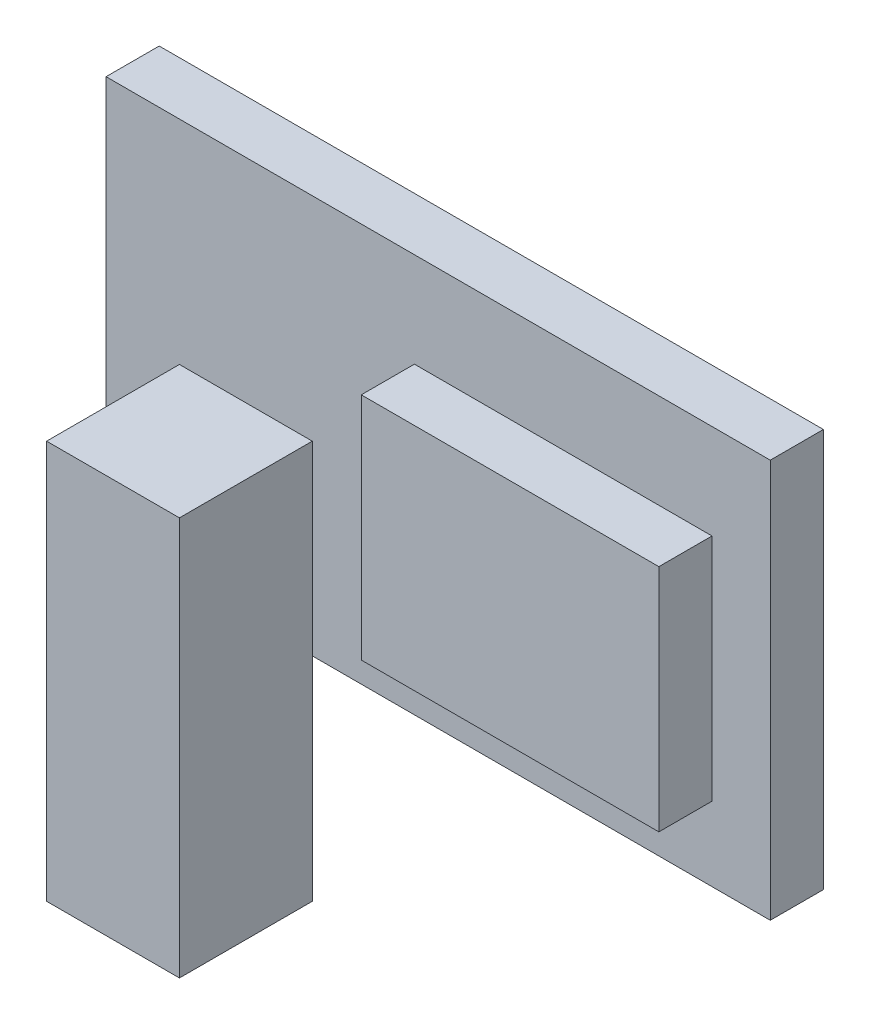
SolidWorks part; units mm, degrees
ref_plane "前视基准面" through (0, 0, 0) normal (0, 0, 1) x (1, 0, 0)
ref_plane "上视基准面" through (0, 0, 0) normal (0, 1, 0) x (1, 0, 0)
ref_plane "右视基准面" through (0, 0, 0) normal (1, 0, 0) x (0, 0, -1)
sketch "草图2" plane through (0, 0, 0) normal (0, 0, 1) x (1, 0, 0)
  line L1 (-14.3456, 4.0965) -> (10.6544, 4.0965)
  line L2 (-14.3456, 4.0965) -> (-14.3456, -10.9035)
  line L3 (-14.3456, -10.9035) -> (10.6544, -10.9035)
  line L4 (10.6544, 4.0965) -> (10.6544, -10.9035)
  dimension "D1" = 25
  dimension "D2" = 15
extrude "凸台-拉伸1" add sketch "草图2" along normal blind 2
sketch "草图3" plane through (0, 0, 2) normal (0, 0, 1) x (1, 0, 0)
  line L0 (-14.3456, -10.9035) -> (10.6544, -10.9035) construction
  line L1 (-11.5842, -3.9035) -> (-6.5842, -3.9035)
  line L2 (-11.5842, -3.9035) -> (-11.5842, -10.9035)
  line L3 (-11.5842, -10.9035) -> (-6.5842, -10.9035)
  line L4 (-6.5842, -3.9035) -> (-6.5842, -10.9035)
  dimension "D1" = 5
  dimension "D2" = 7
sketch "草图4" plane through (0, -10.9035, 0) normal (0, -1, 0) x (1, 0, 0)
  line L0 (-11.5842, 2) -> (-11.5842, 7)
  line L1 (-11.5842, 2) -> (-6.5842, 2) construction
  line L2 (-11.5842, 7) -> (-6.5842, 7)
  line L3 (-6.5842, 7) -> (-6.5842, 2)
  line L4 (-11.507, 2) -> (-6.5842, 2)
  line L5 (-9.0842, 7) -> (-9.0456, 2) construction
  line L6 (-11.5842, 4.5) -> (-6.5842, 4.5) construction
  circle A0 centre (-9.0649, 4.5) radius 1.75
  line M4 (10.6544, 2) -> (-14.3456, 2)
  dimension "D2" = 3.5
  dimension "D1" = 5
extrude "凸台-拉伸2" add sketch "草图4" against normal blind 7 contours L3 L2 L0 A0 M4 region at (-11.5135, -10.9035, 4.5)
sketch "草图5" plane through (0, -3.9035, 0) normal (0, 1, 0) x (1, 0, 0)
  line L4 (-6.5842, -7) -> (-6.5842, -2)
  line L5 (-6.5842, -2) -> (-11.5842, -2)
  line L6 (-11.5842, -2) -> (-11.5842, -7)
  line L7 (-11.5842, -7) -> (-6.5842, -7)
  line L8 (-6.5842, -7) -> (-6.5842, -2)
  line L9 (-6.5842, -2) -> (-11.5842, -2)
  line L10 (-11.5842, -2) -> (-11.5842, -7)
  line L11 (-11.5842, -7) -> (-6.5842, -7)
  dimension "D1" = 0
extrude "凸台-拉伸3" add sketch "草图5" against normal blind 2
extrude "凸台-拉伸4" add sketch "草图4<3>" along normal blind 2 contours L3 L2 L0 A0 M4 region at (-11.5135, -10.9035, 4.5)
sketch "草图4<3>" plane through (0, -10.9035, 0) normal (0, -1, 0) x (1, 0, 0) same geometry as "草图4"
sketch "草图7" plane through (0, 0, 2) normal (0, 0, 1) x (1, 0, 0)
  line L1 (-2.7398, 0.5286) -> (8.4613, 0.5286)
  line L2 (-2.7398, 0.5286) -> (-2.7398, -8.1173)
  line L3 (-2.7398, -8.1173) -> (8.4613, -8.1173)
  line L4 (8.4613, 0.5286) -> (8.4613, -8.1173)
extrude "凸台-拉伸5" add sketch "草图7" along normal blind 2
extrude "凸台-拉伸6" add sketch "草图4<4>" along normal blind 8 contours L3 L2 L0 A0 M4 region at (-11.5135, -10.9035, 4.5)
sketch "草图4<4>" plane through (0, -10.9035, 0) normal (0, -1, 0) x (1, 0, 0) same geometry as "草图4"
